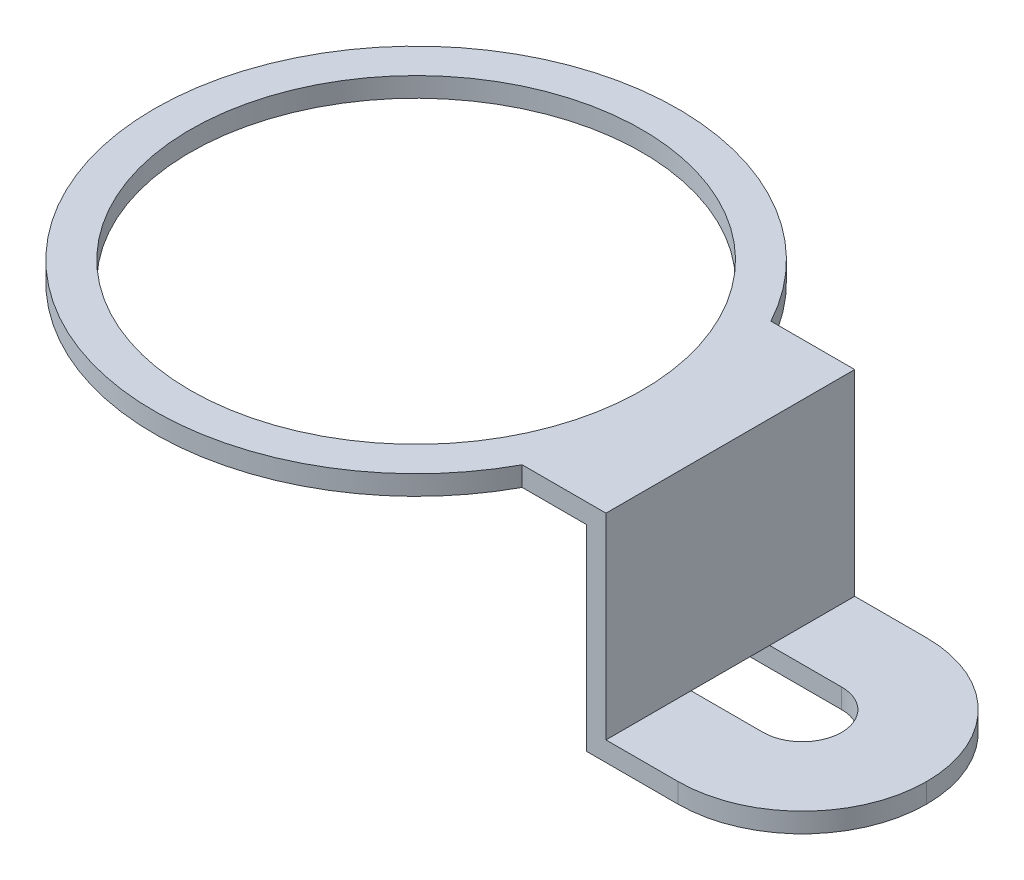
SolidWorks part; units mm, degrees
ref_plane "前视基准面" through (0, 0, 0) normal (0, 0, 1) x (1, 0, 0)
ref_plane "上视基准面" through (0, 0, 0) normal (0, 1, 0) x (1, 0, 0)
ref_plane "右视基准面" through (0, 0, 0) normal (1, 0, 0) x (0, 0, -1)
sketch "草图1" plane through (0, 0, 0) normal (0, 1, 0) x (1, 0, 0)
  line L0 (-77.6751, 0) -> (79.1379, 0) construction
  line L1 (0, 39.057) -> (0, -47.8338) construction
  line L2 (3.5199, 1.9) -> (10, 1.9)
  line L3 (3.5199, -1.9) -> (10, -1.9)
  line L4 (10, 12.8834) -> (10, -14.4726) construction
  line L5 (10, 0) -> (8.5, 0) construction
  line L6 (10, -0.6) -> (8.5, -0.6)
  line L7 (10, 0.6) -> (8.5, 0.6)
  circle A0 centre (0, 0) radius 3.45
  arc A1 (10, 1.9) -> (10, -1.9) centre (10, 0) cw
  arc A2 (10, -0.6) -> (10, 0.6) centre (10, 0) ccw
  arc A3 (8.5, 0.6) -> (8.5, -0.6) centre (8.5, 0) ccw
  arc A4 (3.5199, -1.9) -> (3.5199, 1.9) centre (0, 0) cw
  point P14 (9.25, 0)
  dimension "D1" = 6.9
  dimension "D2" = 1.9
  dimension "D5" = 4
  dimension "D3" = 1.2
  dimension "D4" = 10
  dimension "D6" = 1.5
extrude "凸台-拉伸1" add sketch "草图1" along normal blind 0.3
sketch "草图2" plane through (0, 0.3, 0) normal (0, 1, 0) x (1, 0, 0)
  line L1 (4.5, 3.411) -> (12.8786, 3.411)
  line L2 (4.5, 3.411) -> (4.5, -3.5028)
  line L3 (4.5, -3.5028) -> (12.8786, -3.5028)
  line L4 (12.8786, 3.411) -> (12.8786, -3.5028)
  dimension "D1" = 4.5
extrude "切除-拉伸1" cut sketch "草图2" against normal blind 10
sketch "草图3" plane through (0, 0, 1.9) normal (0, 0, 1) x (1, 0, 0)
  line L0 (4.5, 0.3) -> (4.8, 0.3)
  line L1 (4.8, 0.3) -> (4.8, -2.7)
  line L2 (4.8, -2.7) -> (7.8, -2.7)
  line L3 (4.5, 0) -> (4.5, 0)
  line L4 (4.5, 0) -> (4.5, -3)
  line L5 (4.5, -3) -> (7.8, -3)
  line L6 (4.5, 0) -> (4.5, 0.3) construction
  line L7 (7.8, -3) -> (7.8, -2.7)
  line L8 (4.5, 0) -> (4.5, 0.3)
  dimension "D1" = 3
  dimension "D2" = 3
  dimension "D3" = 0.3
extrude "凸台-拉伸2" add sketch "草图3" against normal up to surface (3.8 mm away) up to face at (4.01, 0.15, -1.9)
fillet "圆角1" radius 1.9 2 edges at (7.8, -2.85, -1.9) (7.8, -2.85, 1.9)
sketch "草图4" plane through (0, -2.7, 0) normal (0, 1, 0) x (1, 0, 0)
  line L0 (-4.9036, 0) -> (9.1096, 0) construction
  line L1 (5.9, 0) -> (4.4, 0) construction
  line L2 (5.9, -0.6) -> (4.4, -0.6)
  line L3 (5.9, 0.6) -> (4.4, 0.6)
  arc A0 (5.9, -0.6) -> (5.9, 0.6) centre (5.9, 0) ccw
  arc A1 (4.4, 0.6) -> (4.4, -0.6) centre (4.4, 0) ccw
  arc A2 (7.8, 0) -> (5.9, 1.9) centre (5.9, 0) ccw construction
  point P5 (5.15, 0)
  dimension "D1" = 1.2
  dimension "D2" = 1.5
extrude "切除-拉伸2" cut sketch "草图4" against normal blind 10
